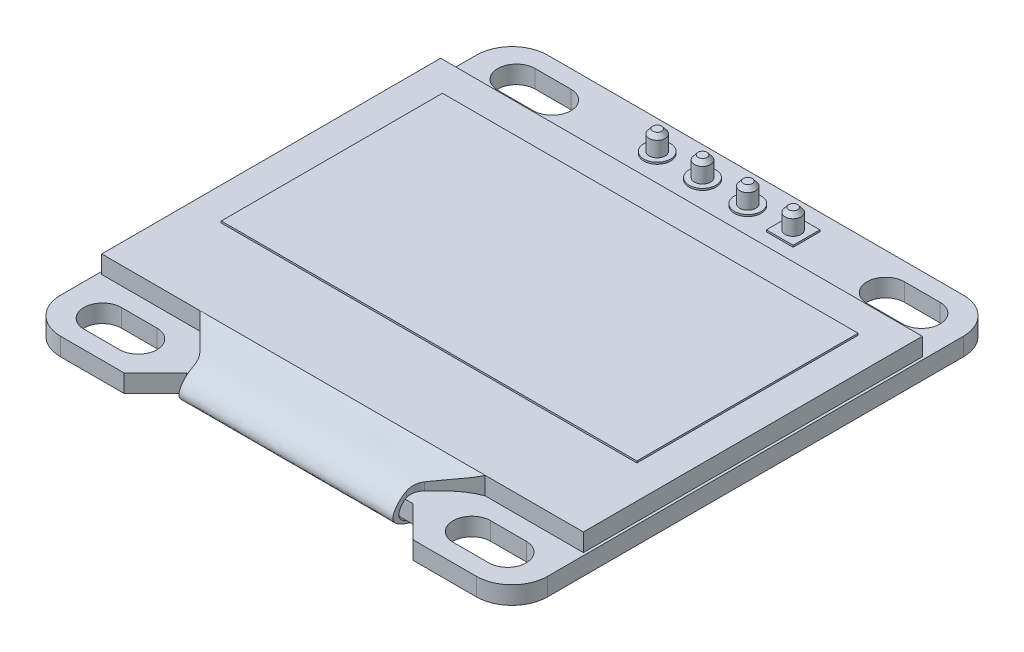
SolidWorks part; units mm, degrees
ref_plane "Front Plane" through (0, 0, 0) normal (0, 0, 1) x (1, 0, 0)
ref_plane "Top Plane" through (0, 0, 0) normal (0, 1, 0) x (1, 0, 0)
ref_plane "Right Plane" through (0, 0, 0) normal (1, 0, 0) x (0, 0, -1)
sketch "Sketch1" plane through (0, 0, 0) normal (0, 1, 0) x (1, 0, 0)
  line L0 (8.1013, -13.65) -> (11.65, -13.65)
  line L1 (-11.65, -13.65) -> (-8.1013, -13.65)
  line L2 (-13.65, -11.65) -> (-13.65, 11.65)
  line L3 (-11.65, 13.65) -> (11.65, 13.65)
  line L4 (13.65, -11.65) -> (13.65, 11.65)
  line L5 (9.35, 10.55) -> (11.35, 10.55)
  line L6 (11.35, 12.65) -> (9.35, 12.65)
  line L8 (-9.35, -10.55) -> (-11.35, -10.55)
  line L9 (-11.35, -12.65) -> (-9.35, -12.65)
  line L10 (11.35, -12.65) -> (9.35, -12.65)
  line L11 (9.35, -10.55) -> (11.35, -10.55)
  line L13 (-6.3513, -11.9) -> (-8.1013, -13.65)
  line L15 (6.3513, -11.9) -> (8.1013, -13.65)
  line L18 (6.3513, -11.9) -> (-6.3513, -11.9)
  line L19 (-11.35, 12.65) -> (-9.35, 12.65)
  line L21 (-9.35, 10.55) -> (-11.35, 10.55)
  arc A0 (11.65, -13.65) -> (13.65, -11.65) centre (11.65, -11.65) ccw
  arc A1 (-13.65, 11.65) -> (-11.65, 13.65) centre (-11.65, 11.65) cw
  arc A2 (-11.65, -13.65) -> (-13.65, -11.65) centre (-11.65, -11.65) cw
  arc A3 (11.65, 13.65) -> (13.65, 11.65) centre (11.65, 11.65) cw
  arc A4 (-9.35, 10.55) -> (-9.35, 12.65) centre (-9.35, 11.6) ccw
  arc A5 (-11.35, 12.65) -> (-11.35, 10.55) centre (-11.35, 11.6) ccw
  arc A6 (11.35, 12.65) -> (11.35, 10.55) centre (11.35, 11.6) cw
  arc A7 (9.35, 10.55) -> (9.35, 12.65) centre (9.35, 11.6) cw
  arc A8 (-11.35, -12.65) -> (-11.35, -10.55) centre (-11.35, -11.6) cw
  arc A9 (-9.35, -10.55) -> (-9.35, -12.65) centre (-9.35, -11.6) cw
  arc A10 (9.35, -10.55) -> (9.35, -12.65) centre (9.35, -11.6) ccw
  arc A11 (11.35, -12.65) -> (11.35, -10.55) centre (11.35, -11.6) ccw
  dimension "D1" = 2
extrude "Boss-Extrude1" add sketch "Sketch1" along normal blind 1
sketch "Sketch2" plane through (0, 1, 0) normal (0, 1, 0) x (1, 0, 0)
  line L1 (-13.5, -9.5) -> (13.5, -9.5)
  line L2 (-13.5, -9.5) -> (-13.5, 9.5)
  line L3 (-13.5, 9.5) -> (13.5, 9.5)
  line L4 (13.5, -9.5) -> (13.5, 9.5)
  line L5 (-13.5, -9.5) -> (13.5, 9.5) construction
  line L6 (-13.5, 9.5) -> (13.5, -9.5) construction
  point P0 (0, 0)
extrude "Boss-Extrude2" add sketch "Sketch2" along normal blind 1
sketch "Sketch3" plane through (0, 1, 0) normal (0, 1, 0) x (1, 0, 0)
  circle A1 centre (1.27, 11.95) radius 0.45
  circle A2 centre (3.81, 11.95) radius 0.45
  circle A3 centre (-3.81, 11.95) radius 0.45
  circle A4 centre (-1.27, 11.95) radius 0.45
extrude "Cut-Extrude1" cut sketch "Sketch3" against normal blind 1
sketch "Sketch4" plane through (0, 1, 0) normal (0, 1, 0) x (1, 0, 0)
  line L1 (3.06, 11.2) -> (4.56, 11.2)
  line L2 (3.06, 11.2) -> (3.06, 12.7)
  line L3 (3.06, 12.7) -> (4.56, 12.7)
  line L4 (4.56, 11.2) -> (4.56, 12.7)
  line L5 (3.06, 11.2) -> (4.56, 12.7) construction
  line L6 (3.06, 12.7) -> (4.56, 11.2) construction
  circle A0 centre (-3.81, 11.95) radius 0.75
  circle A1 centre (-1.27, 11.95) radius 0.75
  circle A2 centre (1.27, 11.95) radius 0.75
  circle A3 centre (-3.81, 11.95) radius 0.45
  circle A4 centre (-1.27, 11.95) radius 0.45
  circle A5 centre (1.27, 11.95) radius 0.45
  circle A6 centre (3.81, 11.95) radius 0.45
  point P9 (3.81, 11.95)
extrude "Boss-Extrude3" add sketch "Sketch4" along normal blind 0.1
sketch "Sketch5" plane through (0, 0, 0) normal (0, -1, 0) x (1, 0, 0)
  line L2 (-5.08, -13.22) -> (5.08, -13.22)
  line L3 (-5.08, -13.22) -> (-5.08, -10.68)
  line L4 (-5.08, -10.68) -> (5.08, -10.68)
  line L5 (5.08, -13.22) -> (5.08, -10.68)
extrude "Boss-Extrude4" [suppressed] add sketch "Sketch5" along normal blind 7
sketch "Sketch6" plane through (0, 1, 0) normal (0, 1, 0) x (1, 0, 0)
  circle A0 centre (-3.81, 11.95) radius 0.45
  circle A1 centre (-1.27, 11.95) radius 0.45
  circle A2 centre (1.27, 11.95) radius 0.45
  circle A3 centre (3.81, 11.95) radius 0.45
extrude "Cut-Extrude2" [suppressed] cut sketch "Sketch6" against normal blind 14
chamfer "Chamfer1" [suppressed] distance 0.2 angle 45
ref_plane "Plane1" through (0, 0, 0) normal (1, 0, 0) x (0, 0, -1)
sketch "Sketch7" plane through (0, 0, 0) normal (1, 0, 0) x (0, 0, -1)
  line L0 (-11.65, 0) -> (11.65, 0) construction
  line L1 (-8.678, 0.1596) -> (-7.8917, 0)
  line L2 (-9.5, 2) -> (-9.1476, 1.2975)
  line L3 (-9.1476, 1.2975) -> (-9.5, 1)
  spline S0 degree 3 poles (-9.5, 2) (-10.4175, 1.6726) (-12.0091, 1.9306) (-12.9051, 0.2218) (-11.6181, -0.2697) (-10.0945, -0.5196) (-8.7544, 0.0355) (-7.8917, 0) knots 0 0 0 0 0.358818 0.423987 0.561263 0.69479 1 1 1 1
  spline S1 degree 3 poles (-9.5, 1) (-10.0101, 1.2561) (-10.8828, 1.2507) (-12.0432, 1.2175) (-12.562, 0.2834) (-11.5585, -0.2056) (-10.3288, -0.2409) (-9.3445, 0.0586) (-8.678, 0.1596) knots 0 0 0 0 0.234866 0.370761 0.452734 0.595151 0.70944 1 1 1 1
extrude "Boss-Extrude5" add sketch "Sketch7" along normal blind 6 and the other way blind 6
chamfer "Chamfer2" distance 2 angle 45 2 edges at (-6, 1.5, 9.5) (6, 1.5, 9.5)
fillet "Fillet1" radius 1 2 edges at (6, 1.4164, 11.5) (-6, 1.4164, 11.5)
sketch "Sketch8" plane through (0, 0, 0) normal (0, -1, 0) x (1, 0, 0)
  line L0 (2.4, 0.8) -> (1.6, 0.8)
  line L1 (0.4, 0.8) -> (-0.4, 0.8)
  line L2 (0.4, 0.8) -> (0.4, -0.8)
  line L3 (0.4, -0.8) -> (-0.4, -0.8)
  line L4 (-0.4, 0.8) -> (-0.4, -0.8)
  line L5 (0.4, 0.8) -> (-0.4, -0.8) construction
  line L6 (0.4, -0.8) -> (-0.4, 0.8) construction
  line L7 (2.4, 0.8) -> (2.4, -0.8)
  line L8 (2.4, -0.8) -> (1.6, -0.8)
  line L9 (1.6, 0.8) -> (1.6, -0.8)
  line L10 (2.4, 0.8) -> (1.6, -0.8) construction
  line L11 (2.4, -0.8) -> (1.6, 0.8) construction
  line L12 (4.4, 0.8) -> (3.6, 0.8)
  line L13 (4.4, 0.8) -> (4.4, -0.8)
  line L14 (4.4, -0.8) -> (3.6, -0.8)
  line L15 (3.6, 0.8) -> (3.6, -0.8)
  line L16 (4.4, 0.8) -> (3.6, -0.8) construction
  line L17 (4.4, -0.8) -> (3.6, 0.8) construction
  line L18 (6.4, 0.8) -> (5.6, 0.8)
  line L19 (6.4, 0.8) -> (6.4, -0.8)
  line L20 (6.4, -0.8) -> (5.6, -0.8)
  line L21 (5.6, 0.8) -> (5.6, -0.8)
  line L22 (6.4, 0.8) -> (5.6, -0.8) construction
  line L23 (6.4, -0.8) -> (5.6, 0.8) construction
  line L24 (8.4, 0.8) -> (7.6, 0.8)
  line L25 (8.4, 0.8) -> (8.4, -0.8)
  line L26 (8.4, -0.8) -> (7.6, -0.8)
  line L27 (7.6, 0.8) -> (7.6, -0.8)
  line L28 (8.4, 0.8) -> (7.6, -0.8) construction
  line L29 (8.4, -0.8) -> (7.6, 0.8) construction
  line L30 (10.4, 0.8) -> (9.6, 0.8)
  line L31 (10.4, 0.8) -> (10.4, -0.8)
  line L32 (10.4, -0.8) -> (9.6, -0.8)
  line L33 (9.6, 0.8) -> (9.6, -0.8)
  line L34 (10.4, 0.8) -> (9.6, -0.8) construction
  line L35 (10.4, -0.8) -> (9.6, 0.8) construction
  line L38 (-10.4, -0.8) -> (-9.6, 0.8) construction
  line L39 (-10.4, 0.8) -> (-9.6, -0.8) construction
  line L40 (-8.4, -0.8) -> (-7.6, 0.8) construction
  line L41 (-8.4, 0.8) -> (-7.6, -0.8) construction
  line L42 (-6.4, -0.8) -> (-5.6, 0.8) construction
  line L43 (-6.4, 0.8) -> (-5.6, -0.8) construction
  line L44 (-4.4, -0.8) -> (-3.6, 0.8) construction
  line L45 (-4.4, 0.8) -> (-3.6, -0.8) construction
  line L46 (-2.4, -0.8) -> (-1.6, 0.8) construction
  line L47 (-2.4, 0.8) -> (-1.6, -0.8) construction
  line L48 (-9.6, 0.8) -> (-9.6, -0.8)
  line L49 (-10.4, -0.8) -> (-9.6, -0.8)
  line L50 (-10.4, 0.8) -> (-10.4, -0.8)
  line L51 (-10.4, 0.8) -> (-9.6, 0.8)
  line L52 (-7.6, 0.8) -> (-7.6, -0.8)
  line L53 (-8.4, -0.8) -> (-7.6, -0.8)
  line L54 (-8.4, 0.8) -> (-8.4, -0.8)
  line L55 (-8.4, 0.8) -> (-7.6, 0.8)
  line L56 (-5.6, 0.8) -> (-5.6, -0.8)
  line L57 (-6.4, -0.8) -> (-5.6, -0.8)
  line L58 (-6.4, 0.8) -> (-6.4, -0.8)
  line L59 (-6.4, 0.8) -> (-5.6, 0.8)
  line L60 (-3.6, 0.8) -> (-3.6, -0.8)
  line L61 (-4.4, -0.8) -> (-3.6, -0.8)
  line L62 (-4.4, 0.8) -> (-4.4, -0.8)
  line L63 (-4.4, 0.8) -> (-3.6, 0.8)
  line L64 (-1.6, 0.8) -> (-1.6, -0.8)
  line L65 (-2.4, -0.8) -> (-1.6, -0.8)
  line L66 (-2.4, 0.8) -> (-2.4, -0.8)
  line L67 (-2.4, 0.8) -> (-1.6, 0.8)
  point P0 (0, 0)
  point P8 (2, 0)
  point P13 (4, 0)
  point P18 (6, 0)
  point P23 (8, 0)
  point P28 (10, 0)
  point P55 (-10, 0)
  point P56 (-8, 0)
  point P57 (-6, 0)
  point P58 (-4, 0)
  point P59 (-2, 0)
  dimension "D1" = 6
extrude "Boss-Extrude6" add sketch "Sketch8" along normal blind 0.6
sketch "Эскиз1" plane through (0, 2, 0) normal (0, 1, 0) x (1, 0, 0)
  line L0 (11.65, 13.65) -> (-11.65, 13.65) construction
  line L1 (11.65, 7.75) -> (-11.65, 7.75)
  line L2 (11.65, 7.75) -> (11.65, -4.65)
  line L3 (11.65, -4.65) -> (-11.65, -4.65)
  line L4 (-11.65, 7.75) -> (-11.65, -4.65)
  line L5 (13.65, -11.65) -> (13.65, 11.65) construction
  line L6 (13.5, -9.5) -> (13.5, 9.5)
  line L7 (13.5, 9.5) -> (-13.5, 9.5)
  line L8 (-13.5, 9.5) -> (-13.5, -9.5)
  line L9 (-13.5, -9.5) -> (-8, -9.5)
  line L10 (-8, -9.5) -> (8, -9.5)
  line L11 (8, -9.5) -> (13.5, -9.5)
  line L12 (13.5, -9.5) -> (13.5, 9.5)
  line L13 (13.5, 9.5) -> (-13.5, 9.5)
  line L14 (-13.5, 9.5) -> (-13.5, -9.5)
  line L15 (-13.5, -9.5) -> (-8, -9.5)
  line L16 (-8, -9.5) -> (8, -9.5)
  line L17 (8, -9.5) -> (13.5, -9.5)
  line L18 (-13.65, 11.65) -> (-13.65, -11.65) construction
  line L19 (8.1013, -13.65) -> (11.65, -13.65) construction
  dimension "D2" = 5.9
  dimension "D3" = 2
  dimension "D4" = 2
  dimension "D5" = 9
  dimension "D1" = 0
extrude "Бобышка-Вытянуть1" add sketch "Эскиз1" along normal blind 0.1 contours L1 L4 L3 L2 region at (0, 2, -1.55)
sketch "Эскиз2" plane through (0, 0, 0) normal (0, -1, 0) x (1, 0, 0)
  line L8 (11.65, 13.65) -> (8.1013, 13.65)
  line L9 (8.1013, 13.65) -> (6.3513, 11.9)
  line L10 (6.3513, 11.9) -> (-6.3513, 11.9)
  line L11 (-6.3513, 11.9) -> (-8.1013, 13.65)
  line L12 (-8.1013, 13.65) -> (-11.65, 13.65)
  line L13 (-13.65, 11.65) -> (-13.65, -11.65)
  line L14 (-11.65, -13.65) -> (11.65, -13.65)
  line L15 (13.65, -11.65) -> (13.65, 11.65)
  line L16 (11.65, 13.65) -> (8.1013, 13.65)
  line L17 (8.1013, 13.65) -> (6.3513, 11.9)
  line L18 (6.3513, 11.9) -> (-6.3513, 11.9)
  line L19 (-6.3513, 11.9) -> (-8.1013, 13.65)
  line L20 (-8.1013, 13.65) -> (-11.65, 13.65)
  line L21 (-13.65, 11.65) -> (-13.65, -11.65)
  line L22 (-11.65, -13.65) -> (11.65, -13.65)
  line L23 (13.65, -11.65) -> (13.65, 11.65)
  circle A0 centre (-3.81, -11.95) radius 0.45 construction
  circle A1 centre (-1.27, -11.95) radius 0.45 construction
  circle A2 centre (1.27, -11.95) radius 0.45 construction
  circle A3 centre (3.81, -11.95) radius 0.45 construction
  arc A4 (13.65, 11.65) -> (11.65, 13.65) centre (11.65, 11.65) ccw
  arc A5 (-11.65, 13.65) -> (-13.65, 11.65) centre (-11.65, 11.65) ccw
  arc A6 (-13.65, -11.65) -> (-11.65, -13.65) centre (-11.65, -11.65) ccw
  arc A7 (11.65, -13.65) -> (13.65, -11.65) centre (11.65, -11.65) ccw
  arc A8 (13.65, 11.65) -> (11.65, 13.65) centre (11.65, 11.65) ccw
  arc A9 (-11.65, 13.65) -> (-13.65, 11.65) centre (-11.65, 11.65) ccw
  arc A10 (-13.65, -11.65) -> (-11.65, -13.65) centre (-11.65, -11.65) ccw
  arc A11 (11.65, -13.65) -> (13.65, -11.65) centre (11.65, -11.65) ccw
  circle A12 centre (-3.81, -11.95) radius 0.45
  circle A13 centre (-1.27, -11.95) radius 0.45
  circle A14 centre (1.27, -11.95) radius 0.45
  circle A15 centre (3.81, -11.95) radius 0.45
  dimension "D1" = 0
extrude "Бобышка-Вытянуть2" add sketch "Эскиз2" along normal blind 8.9 and the other way blind 2.2 contours A14 | A13 | A12 | A15 region at (-3.81, 0, -11.95) region at (-1.27, 0, -11.95) region at (1.27, 0, -11.95)
chamfer "Фаска1" distance 0.2 angle 51 8 edges at (-3.81, -8.9, -12.4) (-1.27, -8.9, -12.4) (1.27, -8.9, -12.4) (3.81, -8.9, -12.4) (3.81, 2.2, -12.4) (1.27, 2.2, -12.4) (-1.27, 2.2, -12.4) (-3.81, 2.2, -12.4) first distance on face at (-3.81, -8.9, -12.4) first distance on face at (-1.27, -8.9, -12.4) first distance on face at (1.27, -8.9, -12.4) first distance on face at (3.81, -8.9, -12.4) first distance on face at (3.81, 2.2, -12.4) first distance on face at (1.27, 2.2, -12.4) first distance on face at (-1.27, 2.2, -12.4) first distance on face at (-3.81, 2.2, -12.4)
